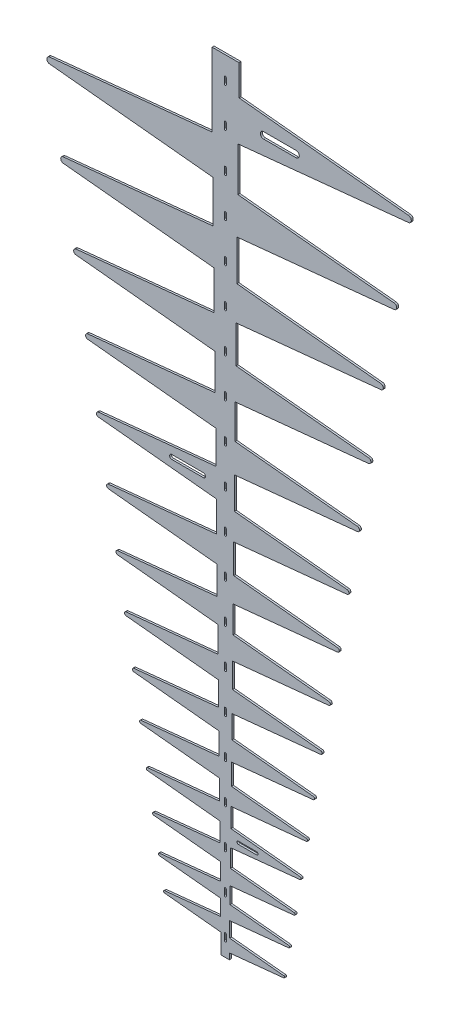
SolidWorks part; units mm, degrees
ref_plane "front" through (0, 0, 0) normal (0, 0, 1) x (1, 0, 0)
ref_plane "top" through (0, 0, 0) normal (0, 1, 0) x (1, 0, 0)
ref_plane "right" through (0, 0, 0) normal (1, 0, 0) x (0, 0, -1)
ref_axis "Axis1" through (0, -2.7284, 0) along (0, 1, 0)
sketch "Sketch5" plane through (0, 0, 0) normal (0, 0, 1) x (1, 0, 0)
  line L0 (-23.3523, 141.8559) -> (10.3275, 141.8559) construction
  line L1 (1.5697, 128.8003) -> (1.5697, 128.4772)
  line L2 (3.2809, 268.534) -> (47.5318, 272.9779)
  line L3 (-1.6391, 128.4772) -> (-1.6391, 126.4452)
  line L4 (47.532, 274.5953) -> (3.5599, 279.0182)
  line L5 (-127.6364, 431.5968) -> (128.8333, 431.5968) construction
  line L6 (1.7074, 139.7462) -> (24.7303, 142.0644)
  line L7 (24.7301, 142.9236) -> (1.8526, 145.2153)
  line L8 (-25.774, 148.8418) -> (-1.9298, 151.2495)
  line L9 (26.8432, 155.0647) -> (2.0107, 157.5532)
  line L10 (-27.9539, 161.5161) -> (-2.096, 164.1532)
  line L11 (29.1313, 168.3486) -> (2.1824, 171.1112)
  line L12 (2.1824, 178.6259) -> (2.1824, 171.1112)
  line L13 (-2.096, 171.5498) -> (-2.096, 164.1532)
  line L14 (-1.7787, 145.579) -> (-25.7737, 147.9826)
  line L15 (-2.096, 171.5498) -> (-30.3853, 174.4498)
  line L17 (2.0107, 164.572) -> (29.131, 167.3378)
  line L18 (-1.9298, 157.948) -> (-1.9298, 151.2495)
  line L19 (1.8526, 151.6314) -> (1.8526, 145.2153)
  line L20 (-1.7787, 145.579) -> (-1.7787, 139.3952)
  line L21 (2.0107, 164.572) -> (2.0107, 157.5532)
  line L22 (-2.6752, 218.9611) -> (-38.7587, 222.5835)
  line L23 (-38.7588, 223.8977) -> (-2.9028, 227.503)
  line L24 (3.5599, 279.0182) -> (3.5599, 291.3645)
  line L25 (-3.4176, 279.7201) -> (-3.4176, 267.8613)
  line L26 (1.8526, 151.6314) -> (26.8436, 154.1549)
  line L27 (-1.9298, 157.948) -> (-27.9531, 160.5558)
  line L28 (-3.4176, 279.7201) -> (-49.5197, 284.3572)
  line L29 (-49.5197, 286.0252) -> (-3.7085, 290.6334)
  line L30 (-30.3826, 175.4608) -> (-2.2721, 178.193)
  line L31 (-2.2721, 178.193) -> (-2.2721, 185.9639)
  line L32 (-2.2721, 185.9639) -> (-32.9222, 189.055)
  line L33 (-32.9221, 190.167) -> (-2.4654, 193.2311)
  line L34 (-1.6391, 126.4452) -> (1.5697, 126.4452)
  line L35 (-2.4654, 193.2311) -> (-2.4654, 201.7887)
  line L36 (-2.4654, 201.7887) -> (-35.7195, 205.1335)
  line L37 (-35.7196, 206.3465) -> (-2.6752, 209.6754)
  line L38 (-2.6752, 209.6754) -> (-2.6752, 218.9611)
  line L39 (2.1824, 178.6259) -> (31.6044, 181.4855)
  line L40 (31.6063, 182.5471) -> (2.3668, 185.496)
  line L41 (2.3668, 185.496) -> (2.3668, 193.7173)
  line L42 (2.3668, 193.7173) -> (34.2917, 196.9291)
  line L43 (34.2917, 198.0917) -> (2.5682, 201.2824)
  line L44 (2.5682, 201.2824) -> (2.5682, 210.2036)
  line L45 (2.5682, 210.2036) -> (37.2102, 213.6934)
  line L46 (37.2099, 214.957) -> (2.7866, 218.4128)
  line L47 (2.7866, 228.0751) -> (40.3748, 231.8546)
  line L48 (40.375, 233.2193) -> (3.0236, 236.9858)
  line L49 (2.7866, 218.4128) -> (2.7866, 228.0751)
  line L50 (-2.9028, 227.503) -> (-2.9028, 237.5834)
  line L51 (-2.9028, 237.5834) -> (-42.0626, 241.5322)
  line L52 (-42.0623, 242.9474) -> (-3.1497, 246.8534)
  line L53 (-3.1497, 246.8534) -> (-3.1497, 257.793)
  line L54 (3.0236, 236.9858) -> (3.0236, 247.473)
  line L55 (3.0236, 247.473) -> (43.7938, 251.5654)
  line L56 (43.7938, 253.0818) -> (3.2809, 257.1476)
  line L57 (3.2809, 257.1476) -> (3.2809, 268.534)
  line L58 (-21.9821, 124.6667) -> (-101.1176, 573.4666) construction
  line L59 (-7.0066, 573.4666) -> (-1.5232, 124.6667) construction
  line L60 (-3.1497, 257.793) -> (-45.6247, 262.0557)
  line L61 (-45.6248, 263.6227) -> (-3.4176, 267.8613)
  line L62 (-3.7085, 290.6334) -> (-3.7085, 303.5279)
  line L63 (3.5599, 291.3645) -> (51.5692, 296.1939)
  line L64 (51.5693, 297.9629) -> (3.8629, 302.7656)
  line L65 (3.8629, 302.7656) -> (3.8629, 316.1633)
  line L66 (-3.7085, 303.5279) -> (-53.7316, 308.5638)
  line L67 (-53.7313, 310.3834) -> (-4.0239, 315.3718)
  line L68 (-4.0239, 315.3718) -> (-4.0239, 329.3438)
  line L69 (-4.0239, 329.3438) -> (-58.3017, 334.8024)
  line L70 (3.8629, 316.1633) -> (55.9555, 321.391)
  line L71 (55.9557, 323.3118) -> (4.1915, 328.5176)
  line L72 (4.1915, 328.5176) -> (4.1915, 343.0603)
  line L73 (-58.3018, 336.7736) -> (-4.3662, 342.1994)
  line L74 (-4.3662, 342.1994) -> (-4.3662, 357.3598)
  line L75 (4.1915, 343.0603) -> (60.723, 348.7472)
  line L76 (60.7229, 350.8196) -> (4.5482, 356.4641)
  line L77 (4.5482, 356.4641) -> (4.5482, 372.2558)
  line L78 (-4.3662, 357.3598) -> (-63.2472, 363.2763)
  line L79 (-63.2471, 365.4497) -> (-4.7375, 371.3236)
  line L80 (-4.7375, 371.3236) -> (-4.7375, 387.7526)
  line L81 (4.5482, 372.2558) -> (65.8976, 378.4148)
  line L82 (65.898, 380.6388) -> (4.9351, 386.7784)
  line L83 (4.9351, 386.7784) -> (4.9351, 403.9209)
  line L84 (-4.7375, 387.7526) -> (-68.6417, 394.1885)
  line L85 (-68.6417, 396.5135) -> (-5.1407, 402.9065)
  line L86 (-5.1407, 402.9065) -> (-5.1407, 420.7498)
  line L87 (4.9351, 403.9209) -> (71.5018, 410.6225)
  line L88 (71.5016, 413.0487) -> (5.3549, 419.6952)
  line L89 (0, 0) -> (0, 573.4666) construction
  line L90 (5.3549, 419.6952) -> (5.3549, 438.2787)
  line L91 (7.0066, 573.4666) -> (1.5232, 124.6667) construction
  line L92 (21.9821, 124.6667) -> (101.1176, 573.4666) construction
  line L93 (-5.1407, 420.7498) -> (-74.4782, 427.717)
  line L94 (1.5697, 126.4452) -> (1.5697, 128.4772)
  line L95 (-74.4784, 430.2442) -> (-5.578, 437.1784)
  line L96 (-5.578, 437.1784) -> (-5.578, 456.5445)
  line L97 (5.3549, 438.2787) -> (77.5849, 445.548)
  line L98 (77.5849, 448.1764) -> (5.8104, 455.3985)
  line L99 (5.8104, 455.3985) -> (5.8104, 475.5613)
  line L100 (-5.578, 456.5445) -> (-80.8213, 464.1157)
  line L101 (-80.8213, 466.8451) -> (-6.0526, 474.3677)
  line L102 (-6.0526, 474.3677) -> (-6.0526, 495.3887)
  line L103 (5.8104, 475.5613) -> (84.1733, 483.4455)
  line L104 (84.173, 486.3266) -> (6.3047, 494.1475)
  line L105 (-6.0526, 495.3887) -> (-87.6871, 503.5879)
  line L106 (-87.6872, 506.5701) -> (-6.5672, 514.7251)
  line L107 (-156.2131, 566.7248) -> (155.1002, 566.7248) construction
  line L108 (6.3047, 516.0191) -> (91.3491, 524.5686)
  line L109 (6.3047, 516.0191) -> (6.3047, 494.1475)
  line L110 (91.3492, 527.6518) -> (6.9242, 536.1449)
  line L111 (6.9242, 536.1449) -> (6.9242, 566.7248)
  line L112 (-6.5672, 514.7251) -> (-6.5672, 537.5021)
  line L113 (-6.5672, 537.5021) -> (-95.1446, 546.413)
  line L114 (-95.1445, 549.6478) -> (-6.9242, 558.5166)
  line L115 (-6.9242, 558.5166) -> (-6.9242, 566.7248)
  line L118 (-1.7787, 139.3952) -> (-23.7459, 137.1834)
  line L119 (-23.7458, 136.3746) -> (-1.6391, 134.1533)
  line L120 (1.7074, 139.7462) -> (1.7074, 133.8171)
  line L121 (1.7074, 133.8171) -> (22.8061, 131.6971)
  line L122 (-6.9242, 566.7248) -> (6.9242, 566.7248)
  line L123 (22.8062, 130.9389) -> (1.5697, 128.8003)
  line L125 (-1.6391, 134.1533) -> (-1.6391, 128.4772)
  line L126 (-1.6391, 128.4772) -> (1.5697, 128.4772) construction
  arc A0 (24.7303, 142.0644) -> (24.7301, 142.9236) centre (24.6871, 142.494) ccw
  arc A1 (-25.7737, 147.9826) -> (-25.774, 148.8418) centre (-25.7306, 148.4122) cw
  arc A2 (26.8436, 154.1549) -> (26.8432, 155.0647) centre (26.7976, 154.6098) ccw
  arc A3 (-27.9531, 160.5558) -> (-27.9539, 161.5161) centre (-27.9049, 161.036) cw
  arc A4 (29.131, 167.3378) -> (29.1313, 168.3486) centre (29.0794, 167.8432) ccw
  arc A5 (-38.7587, 222.5835) -> (-38.7588, 223.8977) centre (-38.6928, 223.2406) cw
  arc A6 (40.3748, 231.8546) -> (40.375, 233.2193) centre (40.3062, 232.537) ccw
  arc A7 (43.7938, 251.5654) -> (43.7938, 253.0818) centre (43.7177, 252.3236) ccw
  arc A8 (47.5318, 272.9779) -> (47.532, 274.5953) centre (47.4506, 273.7866) ccw
  arc A9 (-42.0626, 241.5322) -> (-42.0623, 242.9474) centre (-41.9912, 242.2398) cw
  arc A10 (-45.6247, 262.0557) -> (-45.6248, 263.6227) centre (-45.5461, 262.8392) cw
  arc A11 (-49.5197, 284.3572) -> (-49.5197, 286.0252) centre (-49.4358, 285.1912) cw
  arc A12 (51.5692, 296.1939) -> (51.5693, 297.9629) centre (51.4802, 297.0784) ccw
  arc A13 (-53.7316, 308.5638) -> (-53.7313, 310.3834) centre (-53.64, 309.4736) cw
  arc A14 (55.9555, 321.391) -> (55.9557, 323.3118) centre (55.8592, 322.3514) ccw
  arc A17 (-58.3017, 334.8024) -> (-58.3018, 336.7736) centre (-58.2026, 335.788) cw
  arc A18 (60.723, 348.7472) -> (60.7229, 350.8196) centre (60.6188, 349.7834) ccw
  arc A19 (-30.3853, 174.4498) -> (-30.3826, 175.4608) centre (-30.3335, 174.9552) cw
  arc A20 (-32.9222, 189.055) -> (-32.9221, 190.167) centre (-32.8661, 189.611) cw
  arc A21 (-35.7195, 205.1335) -> (-35.7196, 206.3465) centre (-35.6585, 205.74) cw
  arc A22 (31.6044, 181.4855) -> (31.6063, 182.5471) centre (31.5528, 182.0164) ccw
  arc A23 (34.2917, 196.9291) -> (34.2917, 198.0917) centre (34.2332, 197.5104) ccw
  arc A24 (37.2102, 213.6934) -> (37.2099, 214.957) centre (37.1465, 214.3252) ccw
  arc A25 (-63.2472, 363.2763) -> (-63.2471, 365.4497) centre (-63.138, 364.363) cw
  arc A26 (65.8976, 378.4148) -> (65.898, 380.6388) centre (65.786, 379.5268) ccw
  arc A27 (-68.6417, 394.1885) -> (-68.6417, 396.5135) centre (-68.5246, 395.351) cw
  arc A28 (71.5018, 410.6225) -> (71.5016, 413.0487) centre (71.3797, 411.8356) ccw
  arc A29 (-74.4782, 427.717) -> (-74.4784, 430.2442) centre (-74.3513, 428.9806) cw
  arc A30 (77.5849, 445.548) -> (77.5849, 448.1764) centre (77.4527, 446.8622) ccw
  arc A31 (-80.8213, 464.1157) -> (-80.8213, 466.8451) centre (-80.684, 465.4804) cw
  arc A32 (84.1733, 483.4455) -> (84.173, 486.3266) centre (84.0283, 484.886) ccw
  arc A33 (-87.6871, 503.5879) -> (-87.6872, 506.5701) centre (-87.5373, 505.079) cw
  arc A34 (91.3491, 524.5686) -> (91.3492, 527.6518) centre (91.1941, 526.1102) ccw
  arc A35 (-95.1446, 546.413) -> (-95.1445, 549.6478) centre (-94.9819, 548.0304) cw
  arc A37 (-23.7459, 137.1834) -> (-23.7458, 136.3746) centre (-23.7052, 136.779) ccw
  arc A38 (22.8061, 131.6971) -> (22.8062, 130.9389) centre (22.768, 131.318) cw
  point P28 (0, 0)
  point P69 (-23.1549, 131.318)
  dimension "D10" = 128.4772
  dimension "D11" = 431.5968
  dimension "D8" = 0.381
  dimension "D12" = 142.494
  dimension "D18" = 0.6604
  dimension "D21" = 0.6096
  dimension "D26" = 0.5842
  dimension "D31" = 0.5588
  dimension "D33" = 0.9906
  dimension "D57" = 0.508
  dimension "D58" = 1.6256
  dimension "D59" = 1.5494
  dimension "D60" = 1.4986
  dimension "D61" = 1.4478
  dimension "D62" = 1.3716
  dimension "D63" = 1.3208
  dimension "D64" = 1.27
  dimension "D65" = 1.2192
  dimension "D66" = 1.1684
  dimension "D67" = 1.1176
  dimension "D68" = 1.0922
  dimension "D69" = 1.0414
  dimension "D70" = 0.9652
  dimension "D71" = 0.9144
  dimension "D72" = 0.889
  dimension "D73" = 0.8382
  dimension "D74" = 0.8128
  dimension "D75" = 0.7874
  dimension "D76" = 0.762
  dimension "D9" = 0.7112
  dimension "D14" = 0.6858
  dimension "D19" = 0.635
  dimension "D56" = 0.5334
  dimension "D77" = 0.508
  dimension "D78" = 0.4826
  dimension "D79" = 0.4572
  dimension "D80" = 0.4318
  dimension "D81" = 0.4318
  dimension "D82" = 0.4064
  dimension "D5" = 131.318
  dimension "D6" = 136.779
  dimension "D13" = 148.4122
  dimension "D15" = 0.7
  dimension "D16" = 154.6098
  dimension "D17" = 10
  dimension "D20" = 566.7248
  dimension "D22" = 161.036
  dimension "D23" = 167.8432
  dimension "D24" = 174.9552
  dimension "D25" = 182.0164
  dimension "D27" = 189.611
  dimension "D28" = 205.74
  dimension "D29" = 197.5104
  dimension "D30" = 214.3252
  dimension "D32" = 223.2406
  dimension "D34" = 322.3514
  dimension "D35" = 309.4736
  dimension "D36" = 297.0784
  dimension "D37" = 273.7866
  dimension "D38" = 285.1912
  dimension "D39" = 262.8392
  dimension "D40" = 252.3236
  dimension "D41" = 242.2398
  dimension "D42" = 232.537
  dimension "D43" = 335.788
  dimension "D44" = 349.7834
  dimension "D45" = 379.5268
  dimension "D46" = 364.363
  dimension "D47" = 395.351
  dimension "D48" = 411.8356
  dimension "D49" = 428.9806
  dimension "D50" = 465.4804
  dimension "D51" = 505.079
  dimension "D52" = 446.8622
  dimension "D53" = 484.886
  dimension "D54" = 548.0304
  dimension "D55" = 526.1102
  dimension "D83" = 2.032
extrude "Extrude3" add sketch "Sketch5" along normal blind 0.762
sketch "Sketch7" plane through (0, 0, 0) normal (0, 0, 1) x (1, 0, 0)
  line L0 (-0.4064, 134.3914) -> (-0.4064, 132.1054)
  line L1 (0.4064, 132.1054) -> (0.4064, 134.3914)
  arc A0 (-0.4064, 132.1054) -> (0.4064, 132.1054) centre (0, 132.1054) ccw
  arc A1 (0.4064, 134.3914) -> (-0.4064, 134.3914) centre (0, 134.3914) ccw
  point P5 (0.4064, 133.2484)
  dimension "D2" = 2.286
  dimension "D3" = 133.2484
  dimension "D1" = 0.8128
extrude "Tab 1" cut sketch "Sketch7" along normal through all
sketch "Sketch11" plane through (0, 0, 0) normal (0, 0, 1) x (1, 0, 0)
  line L0 (5.08, 167.2209) -> (12.2936, 167.2209)
  line L1 (12.2936, 168.3131) -> (5.08, 168.3131)
  line L2 (27.6352, 413.07) -> (14.9352, 413.07)
  line L3 (14.9352, 410.5808) -> (27.6352, 410.5808)
  line L4 (-20.889, 284.353) -> (-8.5954, 284.353)
  line L5 (-8.5954, 286.0294) -> (-20.889, 286.0294)
  arc A0 (12.2936, 167.2209) -> (12.2936, 168.3131) centre (12.2936, 167.767) ccw
  arc A1 (5.08, 168.3131) -> (5.08, 167.2209) centre (5.08, 167.767) ccw
  arc A2 (14.9352, 413.07) -> (14.9352, 410.5808) centre (14.9352, 411.8254) ccw
  arc A3 (27.6352, 410.5808) -> (27.6352, 413.07) centre (27.6352, 411.8254) ccw
  arc A4 (-8.5954, 284.353) -> (-8.5954, 286.0294) centre (-8.5954, 285.1912) ccw
  arc A5 (-20.889, 286.0294) -> (-20.889, 284.353) centre (-20.889, 285.1912) ccw
  point P5 (8.6868, 167.2209)
  point P13 (21.2852, 410.5808)
  point P20 (-14.7422, 284.353)
  dimension "D3" = 7.2136
  dimension "D6" = 12.7
  dimension "D10" = 12.2936
  dimension "D1" = 1.0922
  dimension "D2" = 8.6868
  dimension "D4" = 167.767
  dimension "D5" = 2.4892
  dimension "D7" = 411.8254
  dimension "D8" = 21.2852
  dimension "D9" = 1.6764
  dimension "D11" = 14.7422
  dimension "D12" = 285.1912
extrude "Extrude7" cut sketch "Sketch11" along normal through all
pattern_linear "Tab 1 600 x 29" count 29 spacing 15.24 along (0, 1, 0) of "Tab 1"
sketch "Sketch10" plane through (0, 0, 0) normal (0, 0, 1) x (1, 0, 0)
  line L1 (-113.7303, 588.3247) -> (114.3088, 588.3247)
  line L2 (-113.7303, 588.3247) -> (-113.7303, 420.7498)
  line L3 (-113.7303, 420.7498) -> (-5.1407, 420.7498)
  line L4 (114.3088, 588.3247) -> (114.3088, 431.5968)
  line L6 (-5.1407, 420.7498) -> (-5.1407, 431.5968)
  line L7 (-5.1407, 431.5968) -> (114.3088, 431.5968)
  dimension "D1" = 431.5968
extrude "EC-02 Shorten" cut sketch "Sketch10" along normal through all
sketch "Sketch12" [suppressed] plane through (0, 0, 0) normal (1, 0, 0) x (0, 0, -1)
  line L1 (-0.2794, 128.4772) -> (4.8006, 128.4772)
  line L2 (-0.2794, 128.4772) -> (-0.2794, 123.3972)
  line L3 (-0.2794, 123.3972) -> (4.8006, 123.3972)
  line L4 (4.8006, 128.4772) -> (4.8006, 123.3972)
  dimension "D1" = 0.2794
  dimension "D2" = 5.08
  dimension "D3" = 5.08
extrude "Extrude8" [suppressed] cut sketch "Sketch12" against normal mid plane 7.62
